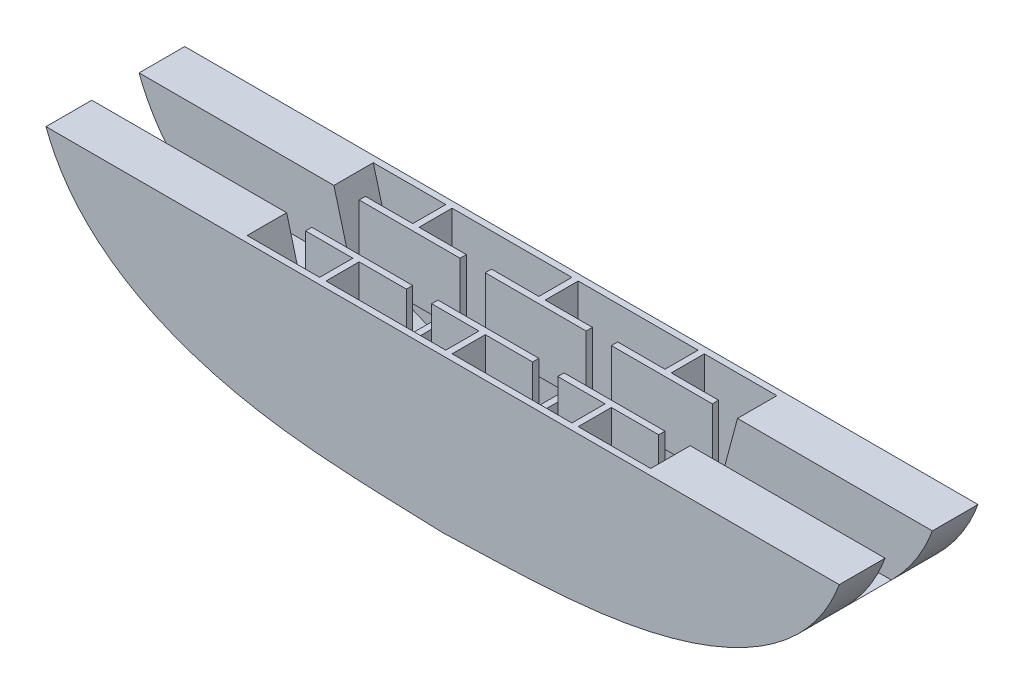
SolidWorks part; units mm, degrees
ref_plane "Front" through (0, 0, 0) normal (0, 0, 1) x (1, 0, 0)
ref_plane "Top" through (0, 0, 0) normal (0, 1, 0) x (1, 0, 0)
ref_plane "Right" through (0, 0, 0) normal (1, 0, 0) x (0, 0, -1)
sketch "Sketch1" plane through (0, 0, 0) normal (0, 0, 1) x (1, 0, 0)
  line L0 (-152.4, 62.23) -> (0, 62.23) construction
  line L1 (-152.4, -62.23) -> (152.4, -62.23) construction
  line L2 (-152.4, -62.23) -> (-152.4, 62.23) construction
  line L3 (-152.4, 62.23) -> (152.4, 62.23) construction
  line L4 (152.4, -62.23) -> (152.4, 62.23) construction
  line L5 (-152.4, -62.23) -> (152.4, 62.23) construction
  line L6 (-152.4, 62.23) -> (152.4, -62.23) construction
  line L7 (-152.4, 62.23) -> (-152.4, -33.02)
  line L8 (-152.4, -33.02) -> (0, -62.23)
  line L9 (0, -62.23) -> (152.4, -32.9764)
  line L10 (152.4, -32.9764) -> (152.4, 62.23)
  line L11 (152.4, 62.23) -> (-152.4, 62.23)
  point P0 (0, 0)
  dimension "D1" = 304.8
  dimension "D2" = 124.46
  dimension "D3" = 95.25
extrude "Boss-Extrude1" add sketch "Sketch1" against normal blind 111.76
ref_plane "Plane1" through (0, 0, -5.08) normal (0, 0, 1) x (1, 0, 0)
sketch "Sketch2" plane through (0, 0, 0) normal (0, 0, 1) x (1, 0, 0)
  line L0 (-152.4, -33.02) -> (-152.4, -13.97) construction
  line L1 (-152.4, 62.23) -> (-152.4, -33.02) construction
  line L2 (152.4, -32.9764) -> (152.4, 62.23) construction
  line L3 (-152.4, -13.97) -> (152.4, -13.97)
  line L4 (-152.4, -13.97) -> (-152.4, 11.43)
  line L5 (-152.4, 11.43) -> (152.4, 11.43)
  line L6 (152.4, -13.97) -> (152.4, 11.43)
  dimension "D1" = 19.05
  dimension "D2" = 25.4
sketch "Sketch5" plane through (0, 0, -5.08) normal (0, 0, 1) x (1, 0, 0)
  line L1 (-152.4, 11.43) -> (152.4, 11.43)
  line L2 (-152.4, 11.43) -> (-152.4, -13.97)
  line L3 (-152.4, -13.97) -> (152.4, -13.97)
  line L4 (152.4, 11.43) -> (152.4, -13.97)
  dimension "D1" = 19.05
  dimension "D2" = 25.4
extrude "Cut-Extrude3" cut sketch "Sketch5" against normal blind 101.6
sketch "Sketch3" plane through (0, 62.23, 0) normal (0, 1, 0) x (1, 0, 0)
  line L0 (152.4, 111.76) -> (-152.4, 111.76) construction
  line L1 (-2.54, 5.08) -> (-99.06, 5.08)
  line L2 (-2.54, 5.08) -> (-2.54, 106.68)
  line L3 (-2.54, 106.68) -> (-99.06, 106.68)
  line L4 (-99.06, 5.08) -> (-99.06, 106.68)
  line L5 (152.4, 0) -> (-152.4, 0) construction
  line L6 (0, 0) -> (0, 111.76) construction
  line L7 (2.54, 106.68) -> (99.06, 106.68)
  line L8 (99.06, 5.08) -> (99.06, 106.68)
  line L9 (2.54, 5.08) -> (99.06, 5.08)
  line L10 (2.54, 5.08) -> (2.54, 106.68)
  line L11 (-152.4, 111.76) -> (-152.4, 0) construction
  line L12 (-104.14, 106.68) -> (-152.4, 106.68)
  line L13 (-104.14, 106.68) -> (-104.14, 5.08)
  line L14 (-104.14, 5.08) -> (-152.4, 5.08)
  line L15 (-152.4, 106.68) -> (-152.4, 5.08)
  line L16 (104.14, 5.08) -> (152.4, 5.08)
  line L17 (152.4, 106.68) -> (152.4, 5.08)
  line L18 (104.14, 106.68) -> (152.4, 106.68)
  line L19 (104.14, 106.68) -> (104.14, 5.08)
  dimension "D1" = 2.54
  dimension "D2" = 96.52
  dimension "D3" = 5.08
  dimension "D4" = 5.08
  dimension "D5" = 5.08
  dimension "D6" = 5.08
  dimension "D7" = 5.08
extrude "Cut-Extrude4" cut sketch "Sketch3" against normal through all both and the other way through all
sketch "Sketch6" plane through (-104.14, 0, 0) normal (-1, 0, 0) x (0, 0, 1)
  line L0 (-5.08, 11.43) -> (-106.68, 11.43) construction
  line L1 (-74.9821, 11.43) -> (-36.8821, 11.43)
  line L2 (-74.9821, 11.43) -> (-74.9821, 62.23)
  line L3 (-74.9821, 62.23) -> (-36.8821, 62.23)
  line L4 (-36.8821, 11.43) -> (-36.8821, 62.23)
  line L5 (-5.08, 62.23) -> (-106.68, 62.23) construction
  dimension "D1" = 38.1
extrude "Cut-Extrude5" cut sketch "Sketch6" against normal up to surface (208.28 mm away) up to face at (104.14, 36.83, -55.88)
ref_plane "Plane2" through (0, 0, -36.8821) normal (0, 0, -1) x (-1, 0, 0)
sketch "Sketch7" plane through (0, 0, -36.8821) normal (0, 0, -1) x (-1, 0, 0)
  line L1 (-40.64, 62.23) -> (40.64, 62.23)
  line L2 (-40.64, 62.23) -> (-40.64, 11.43)
  line L3 (-40.64, 11.43) -> (40.64, 11.43)
  line L4 (40.64, 62.23) -> (40.64, 11.43)
  line L5 (60.96, 62.23) -> (142.24, 62.23)
  line L6 (60.96, 62.23) -> (60.96, 11.43)
  line L7 (60.96, 11.43) -> (142.24, 11.43)
  line L8 (142.24, 62.23) -> (142.24, 11.43)
  line L9 (-142.24, 62.23) -> (-60.96, 62.23)
  line L10 (-142.24, 62.23) -> (-142.24, 11.43)
  line L11 (-142.24, 11.43) -> (-60.96, 11.43)
  line L12 (-60.96, 62.23) -> (-60.96, 11.43)
  dimension "D1" = 38.1
  dimension "D2" = 38.1
  dimension "D3" = 38.1
  dimension "D4" = 38.1
  dimension "D5" = 38.1
  dimension "D6" = 38.1
extrude "Boss-Extrude2" add sketch "Sketch7" against normal blind 5.08
ref_plane "Plane3" through (0, 0, -55.9321) normal (0, 0, -1) x (-1, 0, 0)
mirror "Mirror1" about plane through (0, 0, -55.9321) normal (0, 0, -1) of "Boss-Extrude2"
sketch "Sketch9" plane through (-152.4, 0, 0) normal (-1, 0, 0) x (0, 0, 1)
  line L1 (-111.76, 62.23) -> (-106.68, 62.23)
  line L2 (-111.76, 62.23) -> (-111.76, -33.02)
  line L3 (-111.76, -33.02) -> (-106.68, -33.02)
  line L4 (-106.68, 62.23) -> (-106.68, -33.02)
  line L5 (-5.08, -33.02) -> (0, -33.02)
  line L6 (-5.08, -33.02) -> (-5.08, 62.23)
  line L7 (-5.08, 62.23) -> (0, 62.23)
  line L8 (0, -33.02) -> (0, 62.23)
extrude "Boss-Extrude3" add sketch "Sketch9" along normal blind 10.16
sketch "Sketch10" plane through (152.4, 0, 0) normal (1, 0, 0) x (0, 0, -1)
  line L1 (0, 62.23) -> (5.08, 62.23)
  line L2 (0, 62.23) -> (0, -32.9764)
  line L3 (0, -32.9764) -> (5.08, -32.9764)
  line L4 (5.08, 62.23) -> (5.08, -32.9764)
  line L5 (106.68, -32.9764) -> (111.76, -32.9764)
  line L6 (106.68, -32.9764) -> (106.68, 62.23)
  line L7 (106.68, 62.23) -> (111.76, 62.23)
  line L8 (111.76, -32.9764) -> (111.76, 62.23)
extrude "Boss-Extrude4" add sketch "Sketch10" along normal blind 10.16
sketch "Sketch11" plane through (0, 0, 0) normal (0, 0, 1) x (1, 0, 0)
  line L0 (-162.56, -12.7) -> (-119.6963, -39.2882)
  line L1 (-162.56, -33.02) -> (-162.56, 62.23) construction
  line L2 (-152.4, -33.02) -> (0, -62.23) construction
  line L3 (-119.6963, -39.2882) -> (-152.4, -33.02)
  line L4 (-152.4, -33.02) -> (-162.56, -33.02)
  line L5 (-162.56, -33.02) -> (-162.56, -12.7)
  line L6 (0, -75.9725) -> (0, 75.9725) construction
  line L7 (152.4, -33.02) -> (162.56, -33.02)
  line L8 (119.6963, -39.2882) -> (152.4, -33.02)
  line L9 (162.56, -12.7) -> (119.6963, -39.2882)
  line L10 (162.56, -33.02) -> (162.56, -12.7)
  dimension "D1" = 20.32
extrude "Cut-Extrude7" cut sketch "Sketch11" against normal up to surface (111.76 mm away) up to face at (0, -9.9661, -111.76)
fillet "Fillet1" radius 50.8 9 edges at (-162.56, -12.7, -2.54) (-162.56, -12.7, -109.22) (-119.6963, -39.2882, -109.22) (-119.6963, -39.2882, -2.54) (162.56, -12.7, -109.22) (162.56, -12.7, -2.54) (119.7762, -39.2387, -109.22) (119.7762, -39.2387, -2.54) (0, -62.23, -55.88)
sketch "Sketch12" plane through (0, 0, 0) normal (0, 0, 1) x (1, 0, 0)
  line L0 (-162.56, 62.23) -> (-210.82, 62.23)
  line L1 (-162.56, 62.23) -> (-138.5378, -27.6009)
  line L2 (0, -75.9725) -> (0, 75.9725) construction
  line L3 (162.56, 62.23) -> (210.82, 62.23)
  line L4 (162.56, 62.23) -> (138.5378, -27.6009)
  arc A0 (-138.5378, -27.6009) -> (-210.82, 62.23) centre (-87.1093, 87.7772) cw
  arc A1 (138.5378, -27.6009) -> (210.82, 62.23) centre (87.1093, 87.7772) ccw
  dimension "D1" = 48.26
extrude "Boss-Extrude5" add sketch "Sketch12" against normal up to surface (111.76 mm away) up to face at (0.0134, -14.9837, -111.76)
sketch "Sketch13" plane through (0, 0, 0) normal (1, 0, 0) x (0, 0, -1)
  line L0 (36.8821, 62.23) -> (36.8821, 11.43)
  line L1 (36.8821, 11.43) -> (5.08, 11.43)
  line L2 (5.08, 11.43) -> (5.08, -13.97)
  line L3 (5.08, -13.97) -> (106.68, -13.97)
  line L4 (106.68, -13.97) -> (106.68, 11.43)
  line L5 (106.68, 11.43) -> (74.9821, 11.43)
  line L6 (74.9821, 11.43) -> (74.9821, 62.23)
  line L7 (74.9821, 62.23) -> (36.8821, 62.23)
extrude "Cut-Extrude8" cut sketch "Sketch13" against normal up to surface and the other way up to surface up to face at (-166.2475, -0.5666, -55.88) other way up to face at (166.2475, -0.5666, -55.88)
sketch "Sketch14" plane through (0, 0, -111.76) normal (0, 0, -1) x (-1, 0, 0)
  line L0 (-210.82, 62.23) -> (-319.532, 62.23) construction
  line L1 (-210.82, 62.23) -> (-210.82, 6.858) construction
  line L2 (-210.82, 6.858) -> (-281.686, 6.858) construction
  line L3 (-210.82, 62.23) -> (-210.82, -41.656) construction
  line L4 (-210.82, -41.656) -> (-187.706, -41.656) construction
  line L5 (-210.82, 62.23) -> (-210.82, -56.388) construction
  line L6 (-210.82, -56.388) -> (-102.362, -56.388) construction
  line L7 (-319.532, 62.23) -> (-204.3638, 62.23)
  line L8 (-210.82, 62.23) -> (210.82, 62.23) construction
  line L9 (0.0001, -61.304) -> (0.0001, -56.388)
  line L10 (0, 78.6356) -> (0, -143.442) construction
  line L11 (-0.0001, -61.304) -> (-0.0001, -56.388)
  line L12 (319.532, 62.23) -> (204.3638, 62.23)
  arc A0 (-9.5692, -60.3932) -> (9.5697, -60.3958) centre (0.0071, -10.504) ccw construction
  spline S0 degree 3 poles (0.0001, -61.304) (-63.0357, -58.7298) (-184.1329, -59.3413) (-298.3969, 4.9391) (-319.532, 62.23) knots 0 0 0 0 0.522454 1 1 1 1
  spline S1 degree 3 poles (0.0001, -56.388) (-34.2921, -49.6341) (-117.2936, -40.4496) (-194.6742, 7.6042) (-204.3638, 62.23) knots 0 0 0 0 0.415909 1 1 1 1
  spline S2 degree 3 poles (-0.0001, -61.304) (63.0357, -58.7298) (184.1329, -59.3413) (298.3969, 4.9391) (319.532, 62.23) knots 0 0 0 0 0.522454 1 1 1 1
  spline S3 degree 3 poles (-0.0001, -56.388) (34.2921, -49.6341) (117.2936, -40.4496) (194.6742, 7.6042) (204.3638, 62.23) knots 0 0 0 0 0.415909 1 1 1 1
  dimension "D1" = 108.712
  dimension "D2" = 55.372
  dimension "D3" = 70.866
  dimension "D4" = 103.886
  dimension "D5" = 23.114
  dimension "D6" = 118.618
  dimension "D7" = 108.458
extrude "Boss-Extrude6" add sketch "Sketch14" against normal up to surface (111.76 mm away) contours L11 S3 L12 S2 | S1 L7 S0 L9 up to face at (0.016, -22.2164, 0)
sketch "Sketch15" plane through (0, 0, 0) normal (1, 0, 0) x (0, 0, -1)
  line L0 (36.8821, 62.23) -> (36.8821, 11.43)
  line L1 (36.8821, 11.43) -> (5.08, 11.43)
  line L2 (5.08, 11.43) -> (5.08, -13.97)
  line L3 (5.08, -13.97) -> (106.68, -13.97)
  line L4 (106.68, -13.97) -> (106.68, 11.43)
  line L5 (106.68, 11.43) -> (74.9821, 11.43)
  line L6 (74.9821, 11.43) -> (74.9821, 62.23)
  line L7 (74.9821, 62.23) -> (36.8821, 62.23)
extrude "Cut-Extrude9" cut sketch "Sketch15" along normal blind 241.3 and the other way blind 241.3
sketch "Sketch16" plane through (0, 0, 0) normal (1, 0, 0) x (0, 0, -1)
  line L0 (36.8821, 62.23) -> (74.9821, 62.23)
  line L1 (74.9821, 62.23) -> (74.9821, 11.43)
  line L2 (74.9821, 11.43) -> (36.8821, 11.43)
  line L3 (36.8821, 11.43) -> (36.8821, 62.23)
extrude "Cut-Extrude10" cut sketch "Sketch16" against normal up to surface and the other way up to surface up to face at (-43.3051, -45.7279, -55.88) other way up to face at (43.2842, -45.7287, -55.88)
